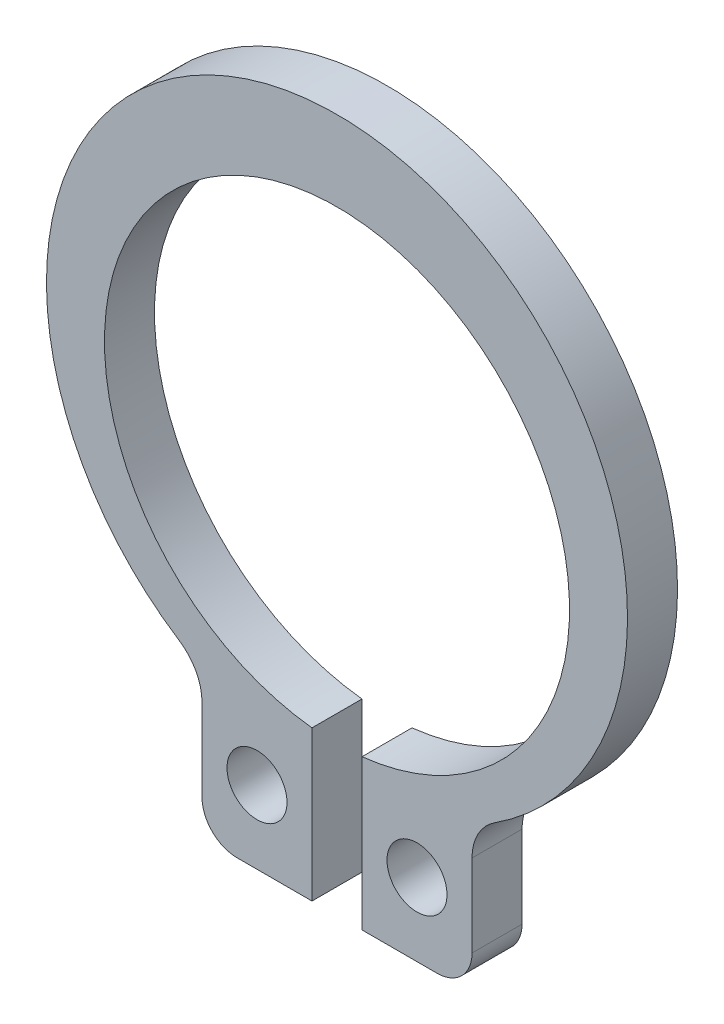
SolidWorks part; units mm, degrees
ref_plane "Front Plane" through (0, 0, 0) normal (0, 0, 1) x (1, 0, 0)
ref_plane "Top Plane" through (0, 0, 0) normal (0, 1, 0) x (1, 0, 0)
ref_plane "Right Plane" through (0, 0, 0) normal (1, 0, 0) x (0, 0, -1)
sketch "BodySke" plane through (0, 0, 0) normal (0, 0, 1) x (1, 0, 0)
  line L0 (0, 0) -> (0, 21.0564) construction
  line L1 (0, 0) -> (0, -11.0385) construction
  line L2 (-0.5, -4.623) -> (-0.5, -7.623)
  line L3 (-0.5, -7.623) -> (-2.7, -7.623)
  line L4 (-2.7, -7.623) -> (-2.7, -4.7045)
  line L5 (2.7, -6.1638) -> (3.9811, -6.1638) construction
  line L7 (0.5, -7.623) -> (2.7, -7.623)
  line L8 (0.5, -4.623) -> (0.5, -7.623)
  line L9 (2.7, -7.623) -> (2.7, -4.7045)
  arc A0 (0.5, -4.623) -> (-0.5, -4.623) centre (0, 0) ccw
  circle A2 centre (-1.6, -6.1638) radius 0.6
  circle A3 centre (1.6, -6.1638) radius 0.6
  arc A4 (2.7, -4.7045) -> (-2.7, -4.7045) centre (0, 0.44) ccw
  dimension "D3" = 5.81
  dimension "Groove_Depth" = 1.6
  dimension "D1" = 0.5
  dimension "D2" = 0.5
  dimension "Thickness" = 1
extrude "BaseBody" add sketch "BodySke" along normal blind 1
fillet "Fillet1" radius 1 2 edges at (2.7, -4.7045, 0.5) (-2.7, -4.7045, 0.5)
fillet "Fillet2" radius 0.7 2 edges at (2.7, -7.623, 0.5) (-2.7, -7.623, 0.5)
equation "\"D1@BodySke\" = \"Thickness@BodySke\" / 2"
equation "\"D2@BodySke\" = \"Thickness@BodySke\" / 2"
equation "\"D3@BodySke\" =  ( \"Groove_Diameter@BodySke\" + 1.45 * \"Groove_Depth@BodySke\" )  / 2"
equation "\"Thickness@BaseBody\" = \"Thickness@BodySke\""
equation "\"D1@Fillet1\" = \"Thickness@BodySke\""
equation "\"D1@Fillet2\" = \"Thickness@BodySke\" * 0.7"
